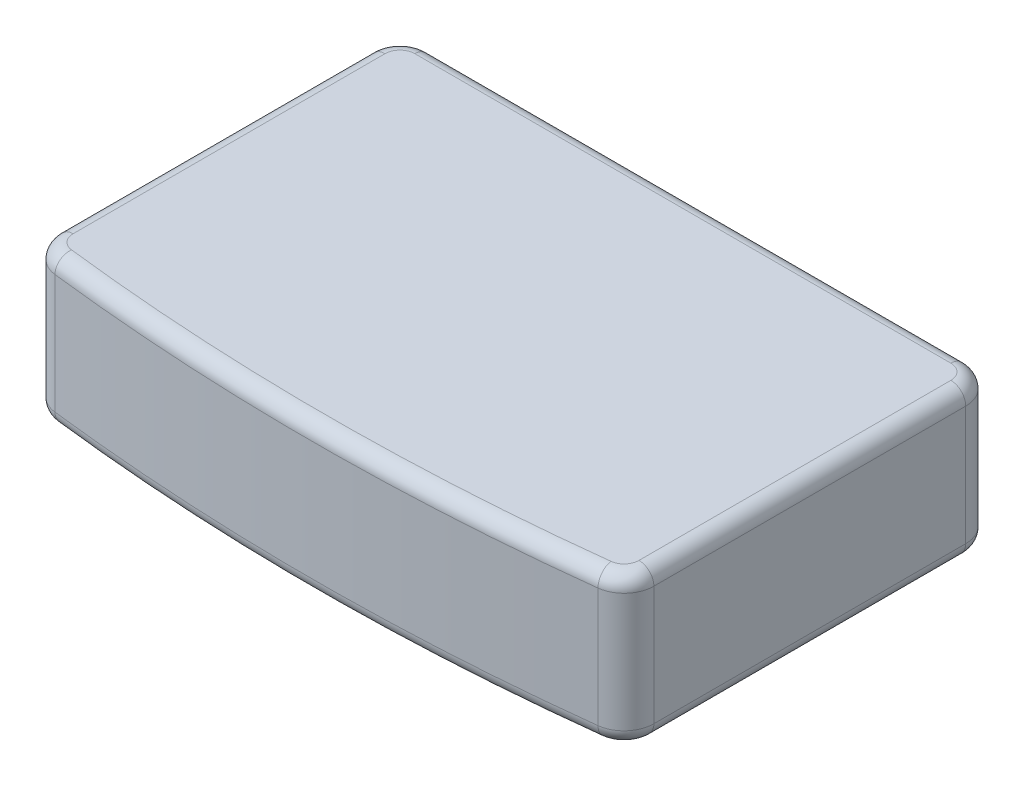
SolidWorks part; units mm, degrees
material "AISI 304"
ref_plane "Front Plane" through (0, 0, 0) normal (0, 0, 1) x (1, 0, 0)
ref_plane "Top Plane" through (0, 0, 0) normal (0, 1, 0) x (1, 0, 0)
ref_plane "Right Plane" through (0, 0, 0) normal (1, 0, 0) x (0, 0, -1)
sketch "Sketch1" plane through (0, 0, 0) normal (0, 1, 0) x (1, 0, 0)
  line L0 (10.5, 0) -> (10.5, 78) construction
  line L2 (0.5, 0.6437) -> (0.5, 13)
  line L3 (0.5, 13) -> (20.5, 13)
  line L4 (20.5, 0.6437) -> (20.5, 13)
  line L5 (10.5, 78) -> (10.5, 4) construction
  circle A0 centre (5.5, 9) radius 1.5
  circle A1 centre (15.5, 9) radius 1.5
  arc A4 (0.5, 0.6437) -> (20.5, 0.6437) centre (10.5, 78) ccw
  dimension "D3" = 3
  dimension "D4" = 3
  dimension "D1" = 20
  dimension "D2" = 10
  dimension "D5" = 5
  dimension "D6" = 4
  dimension "D7" = 5
  dimension "D8" = 9
  dimension "D9" = 13
  dimension "D10" = 74
extrude "Boss-Extrude1" add sketch "Sketch1" along normal blind 5 contours L3 L4 A4 L2
extrude "Cut-Extrude1" cut sketch "Sketch1<3>" along normal blind 3 contours A0 | A1
sketch "Sketch1<3>" plane through (0, 0, 0) normal (0, 1, 0) x (1, 0, 0) same geometry as "Sketch1"
fillet "Fillet1" radius 1 4 edges at (20.5, 2.5, -13) (0.5, 2.5, -13) (20.5, 2.5, -0.6437) (0.5, 2.5, -0.6437)
fillet "Fillet2" radius 0.5 16 edges at (0.7929, 0, -12.7071) (0.5, 0, -6.7639) (20.5, 0, -6.7639) (20.2071, 0, -12.7071) (0.7929, 5, -12.7071) (0.5, 5, -6.7639) (20.5, 5, -6.7639) (20.2071, 5, -12.7071) (10.5, 0, -13) (10.5, 5, -13) (0.7527, 0, -0.8633) (10.5, 0, 0) (20.2473, 0, -0.8633) (0.7527, 5, -0.8633) (10.5, 5, 0) (20.2473, 5, -0.8633)
